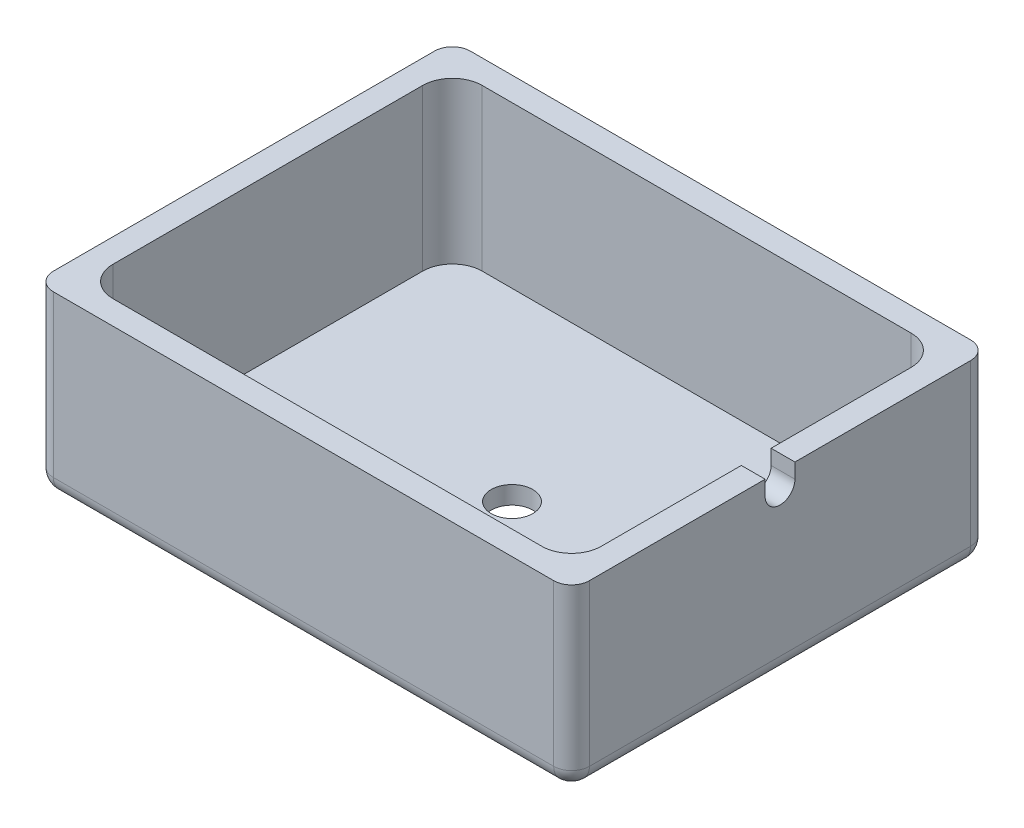
SolidWorks part; units mm, degrees
ref_plane "Plano frontal" through (0, 0, 0) normal (0, 0, 1) x (1, 0, 0)
ref_plane "Plano superior" through (0, 0, 0) normal (0, 1, 0) x (1, 0, 0)
ref_plane "Plano direito" through (0, 0, 0) normal (1, 0, 0) x (0, 0, -1)
sketch "Esboço1" plane through (0, 0, 0) normal (0, 1, 0) x (1, 0, 0)
  line L0 (-41, 31) -> (-41, -31)
  line L1 (-45, 35) -> (45, 35)
  line L2 (-45, 35) -> (-45, -35)
  line L3 (-45, -35) -> (45, -35)
  line L4 (45, 35) -> (45, -35)
  line L5 (-41, -31) -> (41, -31)
  line L6 (41, 31) -> (41, -31)
  line L7 (-41, 31) -> (41, 31)
  circle A0 centre (0, 0) radius 3.5
  dimension "D1" = 7
  dimension "D2" = 35
  dimension "D3" = 45
  dimension "D4" = 70
  dimension "D5" = 90
  dimension "D6" = 4
extrude "Ressalto-extrusão1" add sketch "Esboço1" along normal blind 3 contours L4 L1 L2 L3 L0 L7 L6 L5 | L7 L0 L5 L6 A0 region at (0, 0, -29.972) region at (0, 0, -33.8598)
extrude "Ressalto-extrusão2" add sketch "Esboço1<3>" along normal blind 30 contours L4 L1 L2 L3 L0 L7 L6 L5 region at (0, 0, -33.8598)
sketch "Esboço1<3>" plane through (0, 0, 0) normal (0, 1, 0) x (1, 0, 0) same geometry as "Esboço1"
fillet "Filete1" radius 3 8 edges at (45, 15, 35) (45, 15, -35) (-45, 15, 35) (-45, 15, -35) (45, 0, 0) (0, 0, -35) (0, 0, 35) (-45, 0, 0)
sketch "Esboço2" plane through (45, 0, 0) normal (1, 0, 0) x (0, 0, -1)
  line L0 (32, 30) -> (-32, 30) construction
  line L1 (-2.5, 27.5) -> (-2.5, 30)
  line L2 (-2.5, 30) -> (2.5, 30)
  line L3 (2.5, 30) -> (2.5, 27.5)
  arc A0 (-2.5, 27.5) -> (2.5, 27.5) centre (0, 27.5) ccw
  point P4 (0, 30)
  dimension "D1" = 5
  dimension "D2" = 2.5
extrude "Corte-extrusão1" cut sketch "Esboço2" against normal up to next
fillet "Filete2" radius 5 4 edges at (41, 16.5, 31) (-41, 16.5, 31) (41, 16.5, -31) (-41, 16.5, -31)
